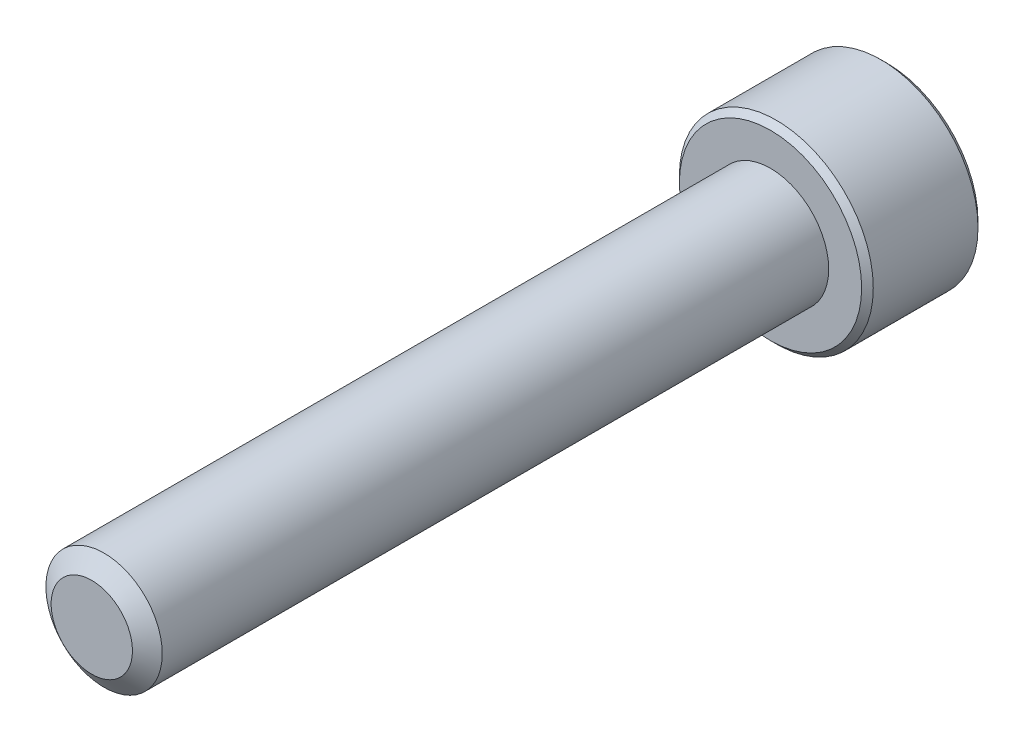
SolidWorks part; units mm, degrees
material "Alloy Steel"
ref_plane "Front Plane" through (0, 0, 0) normal (0, 0, 1) x (1, 0, 0)
ref_plane "Top Plane" through (0, 0, 0) normal (0, 1, 0) x (1, 0, 0)
ref_plane "Right Plane" through (0, 0, 0) normal (1, 0, 0) x (0, 0, -1)
sketch "Sketch1" plane through (0, 0, 0) normal (0, 0, 1) x (1, 0, 0)
  circle A0 centre (0, 0) radius 3
  dimension "OD" = 6
extrude "Extrude1" add sketch "Sketch1" against normal blind 35
sketch "Sketch2" plane through (0, 0, 0) normal (0, 0, 1) x (1, 0, 0)
  circle A0 centre (0, 0) radius 3 construction
  circle A1 centre (0, 0) radius 3
curve "Helix/Spiral1" pitch 1 height 36 turns 36 parameters "pitch"=1
sketch "Sketch3" plane through (0, 0, 0) normal (1, 0, 0) x (0, 0, -1)
  line L0 (-0.875, 3) -> (-0.5, 2.3505)
  line L1 (-0.5, 2.3505) -> (-0.375, 2.3505)
  line L2 (-0.375, 2.3505) -> (0, 3)
  line L3 (-0.875, 3) -> (0, 3)
  line L4 (-0.4375, 3) -> (-0.4375, 2.3505) construction
  line L5 (-0.6875, 2.6752) -> (-0.1875, 2.6752) construction
  line L6 (0, 3) -> (0, -3) construction
  line L7 (0, -3) -> (35, -3) construction
  point P11 (4.5, -3)
  dimension "D1" = 0.125
  dimension "D2" = 0.5
  dimension "D3" = 60
  dimension "D4" = 4.5
sweep "Cut-Sweep1" [suppressed] cut profiles "Sketch3" path "Helix/Spiral1"
sketch "Sketch4" plane through (0, 0, 0) normal (1, 0, 0) x (0, 0, -1)
  line L0 (0.6327, 3) -> (0, 2.0965)
  line L1 (0, 2.0965) -> (0, 3)
  line L2 (0.6327, 3) -> (0, 3)
  line L3 (-0.875, 3) -> (0, 3) construction
  line L4 (0, 0) -> (7.0209, 0) construction
  dimension "D1" = 55
  dimension "D2" = 0.254
revolve "Cut-Revolve1" cut sketch "Sketch4" angle 360 about L4
sketch "Sketch5" [suppressed] plane through (0, 0, 0) normal (1, 0, 0) x (0, 0, -1)
  line L0 (35, -2.3644) -> (35, 2.1406) construction
  line L1 (35, 3) -> (0.1203, 3)
  line L2 (35, 3) -> (35, 0)
  line L3 (35, 0) -> (0.0001, 0)
  line L4 (0.0001, 2.6698) -> (0.0001, 0)
  line L5 (0.1203, 3) -> (0.0001, 2.6698)
  line L6 (0, 0) -> (9.9695, 0) construction
  point P3 (0.0001, 3)
  point P10 (0.0001, 3)
  dimension "D1" = 0.3302
  dimension "Thread min" = 0.0001
  dimension "D3" = 20
revolve "partially thread" [suppressed] add sketch "Sketch5" angle 360 about L6
sketch "Sketch6" plane through (0, 0, -35) normal (0, 0, -1) x (-1, 0, 0)
  circle A0 centre (0, 0) radius 5
  dimension "head dia" = 10
extrude "Extrude2" add sketch "Sketch6" along normal blind 6
sketch "Sketch7" plane through (0, 0, -41) normal (0, 0, -1) x (-1, 0, 0)
  line L1 (0, 2.8868) -> (-2.5, 1.4434)
  line L2 (-2.5, 1.4434) -> (-2.5, -1.4434)
  line L3 (-2.5, -1.4434) -> (0, -2.8868)
  line L4 (0, -2.8868) -> (2.5, -1.4434)
  line L5 (2.5, -1.4434) -> (2.5, 1.4434)
  line L6 (2.5, 1.4434) -> (0, 2.8868)
  circle A0 centre (0, 0) radius 2.5 construction
  dimension "hex dia" = 5
extrude "Cut-Extrude1" cut sketch "Sketch7" against normal blind 3.75
sketch "Sketch8" plane through (0, 0, -41) normal (0, 0, -1) x (-1, 0, 0)
  circle A0 centre (0, 0) radius 2.8868
extrude "Cut-Extrude2" cut sketch "Sketch8" against normal through all draft 45
chamfer "Chamfer1" distance 0.3 angle 45 2 edges at (-5, 0, -41) (-5, 0, -35)
sketch "Sketch9" plane through (0, 0, 0) normal (1, 0, 0) x (0, 0, -1)
  line L0 (0, 3) -> (0, -3) construction
  line L1 (5.5, 3) -> (5.5, -3) construction
  dimension "D1" = 5.5
sketch "Sketch10" plane through (0, 0, 0) normal (1, 0, 0) x (0, 0, -1)
  line L0 (35, 3) -> (35, 0)
  line L1 (35, 3) -> (34.75, 3)
  line L2 (34.75, 3) -> (33.5074, 0)
  line L3 (35, 0) -> (33.5074, 0)
  line L4 (35, 4.7) -> (35, -4.7) construction
  dimension "D1" = 22.5
  dimension "D2" = 0.25
revolve "Revolve1" add sketch "Sketch10" angle 360 about L3
equation "\"D3@Helix/Spiral1\" = \"screw length@Extrude1\"+\"pitch@Helix/Spiral1\""
equation "\"D1@Sketch3\" = \"pitch@Helix/Spiral1\"*.125"
equation "\"D2@Sketch3\" = \"pitch@Helix/Spiral1\"*.5"
equation "\"D1@Cut-Extrude1\" = \"hex dia@Sketch7\"*.75"
equation "\"D1@Chamfer1\" = \"head dia@Sketch6\"*.03"
equation "\"D1@Sketch9\" = \"pitch@Helix/Spiral1\"*5.5"
equation "\"D2@Sketch10\" = \"pitch@Helix/Spiral1\"*.25"
equation "\"D4@Sketch3\" = \"pitch@Helix/Spiral1\"*4.50"
